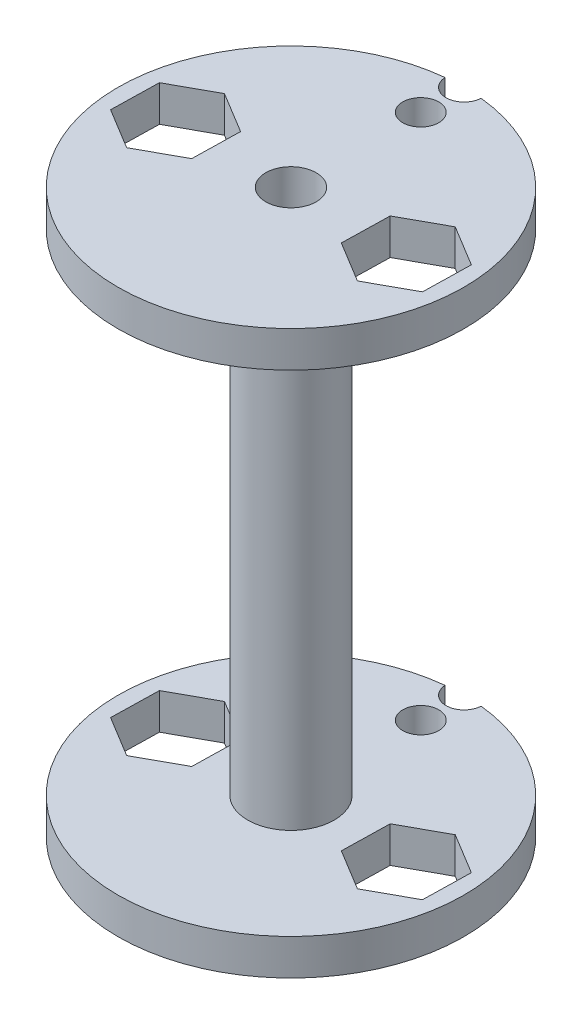
SolidWorks part; units mm, degrees
ref_plane "Front Plane" through (0, 0, 0) normal (0, 0, 1) x (1, 0, 0)
ref_plane "Top Plane" through (0, 0, 0) normal (0, 1, 0) x (1, 0, 0)
ref_plane "Right Plane" through (0, 0, 0) normal (1, 0, 0) x (0, 0, -1)
sketch "Sketch1" plane through (0, 0, 0) normal (0, 1, 0) x (1, 0, 0)
  circle A1 centre (0, 0) radius 12
  circle A2 centre (0, 0) radius 1.75
extrude "Boss-Extrude1" add sketch "Sketch1" along normal blind 2.5
sketch "Sketch2" plane through (0, 2.5, 0) normal (0, 1, 0) x (1, 0, 0)
  circle A0 centre (0, 0) radius 3
  circle A1 centre (0, 0) radius 1.75
sketch "Sketch3" plane through (0, 0, 0) normal (0, -1, 0) x (1, 0, 0)
  line L0 (-5.1613, 1.7213) -> (-8.0713, 3.319)
  line L1 (5.1613, -1.7213) -> (8.0713, -3.319)
  line L2 (8.0713, -3.319) -> (10.91, -1.5977)
  line L3 (10.91, -1.5977) -> (10.8387, 1.7213)
  line L4 (10.8387, 1.7213) -> (7.9287, 3.319)
  line L5 (7.9287, 3.319) -> (5.09, 1.5977)
  line L6 (5.09, 1.5977) -> (5.1613, -1.7213)
  line L7 (-8.0713, 3.319) -> (-10.91, 1.5977)
  line L8 (-10.91, 1.5977) -> (-10.8387, -1.7213)
  line L9 (-10.8387, -1.7213) -> (-7.9287, -3.319)
  line L10 (-7.9287, -3.319) -> (-5.09, -1.5977)
  line L11 (-5.09, -1.5977) -> (-5.1613, 1.7213)
  circle A0 centre (8, 0) radius 2.875 construction
  point P17 (0, 0)
  dimension "D2" = 8
  dimension "D1" = 2
extrude "Cut-Extrude3" cut sketch "Sketch3" against normal blind 2.5
sketch "Sketch4" plane through (0, 2.5, 0) normal (0, 1, 0) x (1, 0, 0)
  circle A0 centre (0, 9) radius 1.25
  circle A1 centre (0, 12) radius 1.25
  circle A2 centre (0, 0) radius 12 construction
  dimension "D1" = 9
extrude "Cut-Extrude4" cut sketch "Sketch4" against normal blind 5
sketch "Sketch5" plane through (0, 2.5, 0) normal (0, 1, 0) x (1, 0, 0)
  circle A0 centre (0, -16.2068) radius 3.1
extrude "Cut-Extrude5" [suppressed] cut sketch "Sketch5" along normal blind 2.5 from surface
extrude "Boss-Extrude2" add sketch "Sketch2" along normal blind 17
mirror "Mirror7" about plane through (0, 19.5, 0) normal (0, 1, 0) of bodies 107
